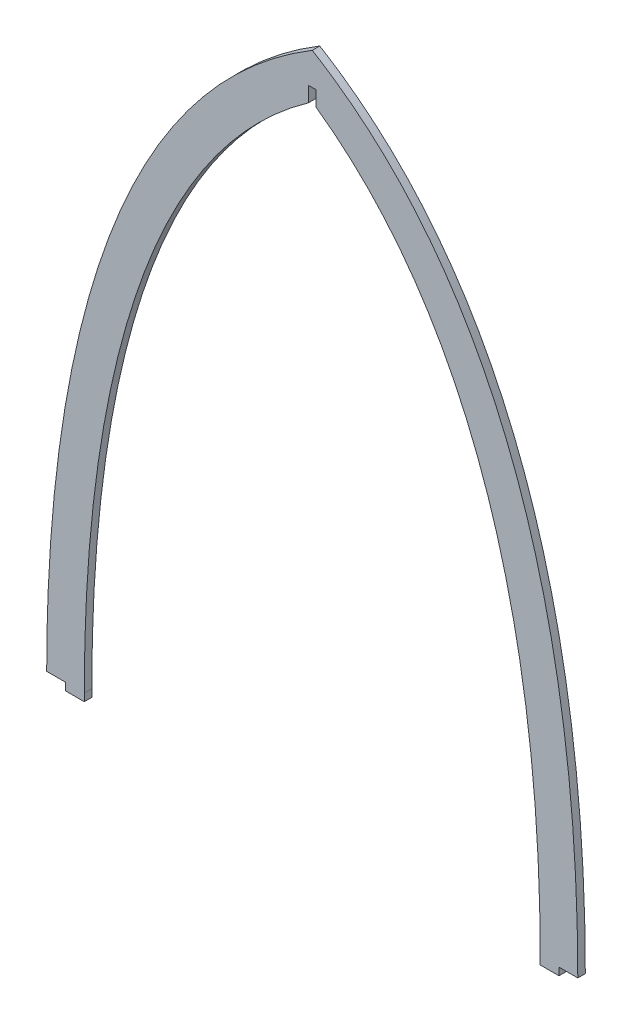
SolidWorks part; units mm, degrees
material "birch 3mm plywood"
ref_plane "Front" through (0, 0, 0) normal (0, 0, 1) x (1, 0, 0)
ref_plane "Top" through (0, 0, 0) normal (0, 1, 0) x (1, 0, 0)
ref_plane "Right" through (0, 0, 0) normal (1, 0, 0) x (0, 0, -1)
sketch "Sketch1" plane through (0, 0, 0) normal (0, 0, 1) x (1, 0, 0)
  line L0 (-106, 162) -> (-98.5, 162)
  line L1 (98.5, 162) -> (106, 162)
  line L2 (-1.5, 410.7938) -> (-1.5, 416.8417)
  line L4 (-1.5, 416.8417) -> (1.5, 416.8417)
  line L6 (1.5, 416.8417) -> (1.5, 410.7938)
  line L7 (91, 162) -> (91, 159)
  line L8 (68.5834, 159) -> (106, 159) construction
  line L9 (91, 159) -> (98.5, 159)
  line L10 (98.5, 159) -> (98.5, 162)
  line L11 (-91, 162) -> (-91, 159)
  line L12 (-106, 159) -> (-68.5834, 159) construction
  line L13 (-91, 159) -> (-98.5, 159)
  line L14 (-98.5, 159) -> (-98.5, 162)
  spline S0 degree 3 poles (731.6974, 2061.492) (-826.2531, -2407.5928) (1400.031, 2486.8597) (-1613.0269, -709.5741) knots -2.608907 -2.608907 -2.608907 -2.608907 2.870697 2.870697 2.870697 2.870697 only from (106, 162) to (0, 429.6834) construction
  spline S1 degree 3 poles (-731.6974, 2061.492) (826.2531, -2407.5928) (-1400.031, 2486.8597) (1613.0269, -709.5741) knots -2.608907 -2.608907 -2.608907 -2.608907 2.870697 2.870697 2.870697 2.870697 only from (-106, 162) to (0, 429.6834) construction
  spline S2 degree 3 poles (106, 162) (106, 251.5112) (88.9481, 376.101) (0, 429.6834) knots 0 0 0 0 1 1 1 1
  spline S3 degree 3 poles (-106, 162) (-106, 251.5112) (-88.9481, 376.101) (0, 429.6834) knots 0 0 0 0 1 1 1 1
  spline S4 degree 1 poles (-91, 162) (0, 411.8417) knots 0 0 1 1 construction
  spline S5 degree 1 poles (91, 162) (0, 411.8417) knots 0 0 1 1 construction
  spline S6 degree 3 poles (-91, 162) (-91, 163.3315) (-90.9924, 165.9839) (-90.9452, 171.374) (-90.8235, 178.2059) (-90.5685, 186.5558) (-90.0716, 197.86) (-89.1348, 212.2691) (-87.4371, 229.859) (-85.099, 247.6019) (-81.0409, 271.2671) (-74.0455, 300.4955) (-62.1021, 333.8333) (-48.8481, 359.2218) (-36.0733, 377.5905) (-25.3557, 390.2872) (-15.418, 399.8913) (-6.8379, 406.9345) (-2.3043, 410.2528) (0, 411.8417) knots 0 0 0 0 0.015113 0.030226 0.060452 0.090678 0.120904 0.181356 0.241808 0.302259 0.362711 0.483615 0.604519 0.725423 0.785874 0.846326 0.906778 0.937004 0.96723 0.96723 0.96723 0.96723 only from (-91, 162) to (-1.5, 410.7938)
  spline S7 degree 3 poles (0, 411.8417) (2.3043, 410.2528) (6.8379, 406.9345) (15.418, 399.8913) (25.3557, 390.2872) (36.0733, 377.5905) (48.8481, 359.2218) (62.1021, 333.8333) (74.0455, 300.4955) (81.0409, 271.2671) (85.099, 247.6019) (87.4371, 229.859) (89.1348, 212.2691) (90.0716, 197.86) (90.5685, 186.5558) (90.8235, 178.2059) (90.9452, 171.374) (90.9924, 165.9839) (91, 163.3315) (91, 162) knots 0 0 0 0 0.030226 0.060452 0.120904 0.181356 0.241808 0.362711 0.483615 0.604519 0.664971 0.725423 0.785874 0.846326 0.876552 0.906778 0.937004 0.952117 0.96723 0.96723 0.96723 0.96723 only from (1.5, 410.7938) to (91, 162)
  dimension "D1" = 5
  dimension "D2" = 7.5
extrude "Boss-Extrude1" add sketch "Sketch1" along normal mid plane 3
